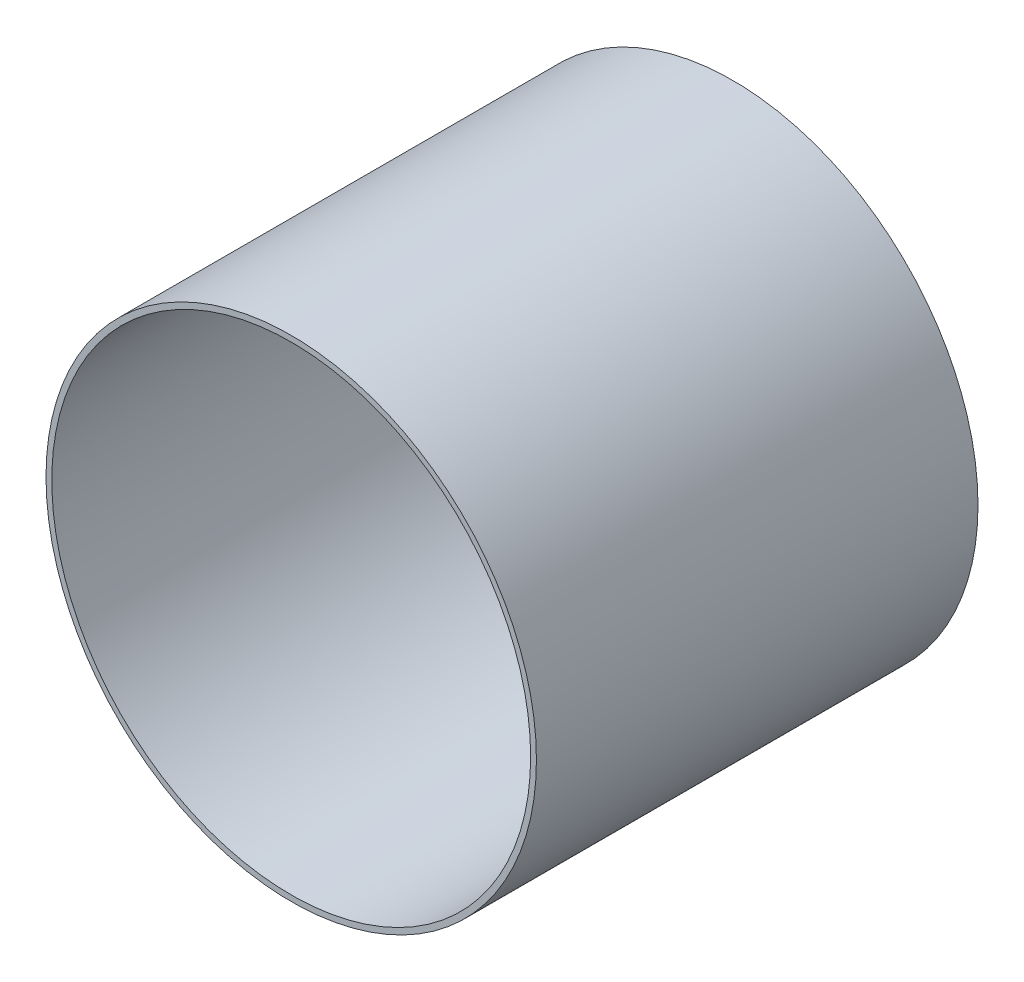
SolidWorks part; units mm, degrees
ref_plane "Front Plane" through (0, 0, 0) normal (0, 0, 1) x (1, 0, 0)
ref_plane "Top Plane" through (0, 0, 0) normal (0, 1, 0) x (1, 0, 0)
ref_plane "Right Plane" through (0, 0, 0) normal (1, 0, 0) x (0, 0, -1)
sketch "Sketch1" plane through (0, 0, 0) normal (0, 0, 1) x (1, 0, 0)
  circle A0 centre (0, 0) radius 63.4746
  circle A1 centre (0, 0) radius 61.976
  dimension "D1" = 123.952
  dimension "D2" = 126.9492
extrude "Boss-Extrude1" add sketch "Sketch1" along normal mid plane 114.3
equation "\"AIRFRAME_OD\"= 5.15in"
equation "\"AIRFRAME_ID\"= 5.00in"
equation "\"FLAT_T\"= 0.125in"
equation "\"NOSE_EXP_L\"= 27in"
equation "\"NOSE_SHOULDER_L\"= 5in"
equation "\"MAIN_L\"= 30in"
equation "\"RECO_COUP_L\"= 10in"
equation "\"RECO_SWITCH_L\"= 2in"
equation "\"DROGUE_L\"= 20in"
equation "\"ATS_FORE_COUP_L\"= 5.5in"
equation "\"ATS_AFT_COUP_L\"= 4.5in"
equation "\"LOWER_L\"= 30in"
equation "\"FIN_N\"= 4"
equation "\"CR_AFT_X\"= 0.5in"
equation "\"CR_FORE_X\"= 9.25in"
equation "\"D1@Sketch1\"=\"COUPLER_ID\""
equation "\"D2@Sketch1\"=\"COUPLER_OD\""
equation "\"D1@Boss-Extrude1\"=\"ATS_AFT_COUP_L\""
equation "\"FIN_ROOT\"= 8in"
equation "\"FIN_X\"= 0.75in"
equation "\"MOTOR_OD\"= 3.091in"
equation "\"MOTOR_ID\"= 3.00in"
equation "\"COUPLER_OD\"= 4.998in"
equation "\"COUPLER_ID\"= 4.88in"
equation "\"RECO_ROD_X\"= 3.5in"
equation "\"ATS_ROD_X\"= 3in"
equation "\"MOTOR_L\"= 14in"
equation "\"MOTOR_LOWER_X\"= 2in"
